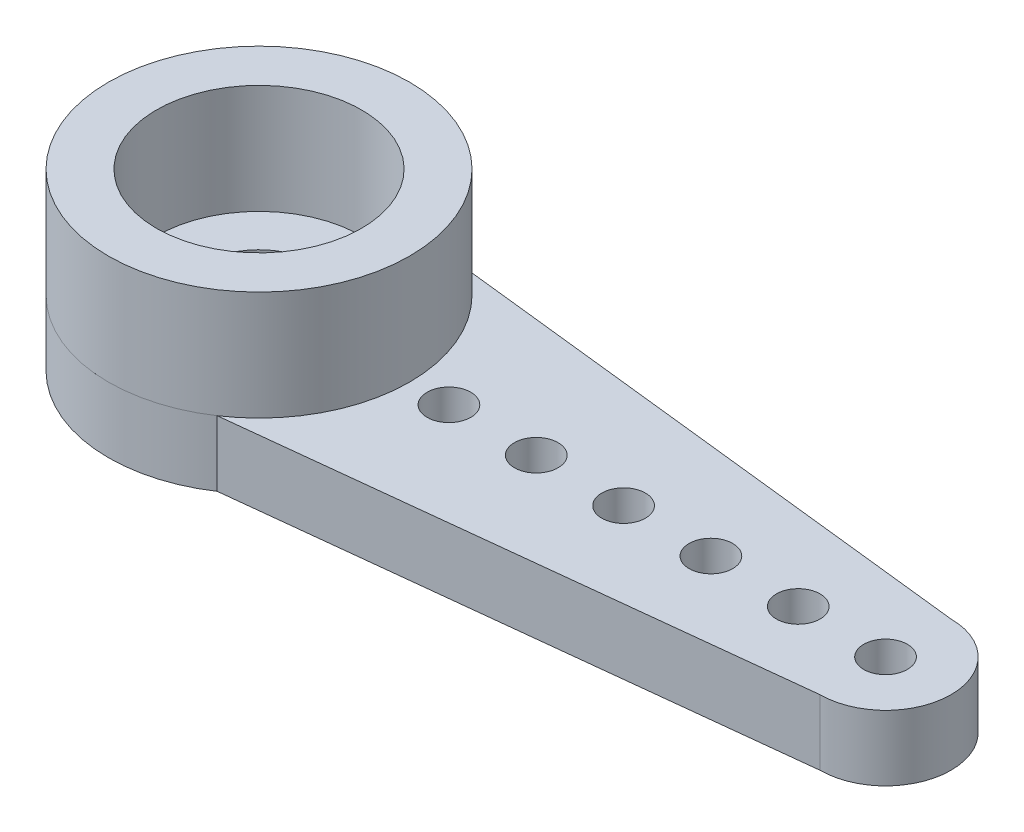
SolidWorks part; units mm, degrees
ref_plane "Front Plane" through (0, 0, 0) normal (0, 0, 1) x (1, 0, 0)
ref_plane "Top Plane" through (0, 0, 0) normal (0, 1, 0) x (1, 0, 0)
ref_plane "Right Plane" through (0, 0, 0) normal (1, 0, 0) x (0, 0, -1)
sketch "Sketch1" plane through (0, 0, 0) normal (0, 1, 0) x (1, 0, 0)
  line L0 (0, 0) -> (15.85, 0) construction
  line L1 (14.35, 1.5) -> (1.8797, 2.8929)
  line L3 (1.9132, -2.8709) -> (14.35, -1.5)
  arc A0 (1.8797, 2.8929) -> (1.9132, -2.8709) centre (0, 0) ccw
  circle A1 centre (0, 0) radius 1.275 construction
  circle A2 centre (0, 0) radius 2.35
  circle A4 centre (12.35, 0) radius 0.5
  circle A5 centre (14.35, 0) radius 0.5
  circle A6 centre (10.35, 0) radius 0.5
  circle A7 centre (8.35, 0) radius 0.5
  circle A9 centre (6.35, 0) radius 0.5
  circle A10 centre (4.35, 0) radius 0.5
  arc A11 (14.35, -1.5) -> (14.35, 1.5) centre (14.35, 0) ccw
  point P5 (0, 0)
  point P23 (0, 0)
  point P24 (0, 0)
  dimension "D1" = 14.35
  dimension "D2" = 2.55
  dimension "D3" = 4.7
  dimension "D4" = 6.9
sketch3d "3DSketch2" plane through (0, 0, 0) normal (0, 0, 1) x (1, 0, 0)
  dimension "D1" = 1.5
extrude "Boss-Extrude1" add sketch "Sketch1" along normal blind 1.5
sketch "Sketch2" plane through (0, 1.5, 0) normal (0, 1, 0) x (1, 0, 0)
  circle A0 centre (0, 0) radius 1.275
  circle A1 centre (0, 0) radius 2.35
  circle A2 centre (0, 0) radius 3.45
extrude "Boss-Extrude3" add sketch "Sketch2" against normal blind 0.5 separate body contours A1 A0 region at (-2.2835, 1.5, 0)
extrude "Boss-Extrude5" add sketch "Sketch2<7>" along normal blind 2.5 separate body contours A2 A1 region at (-3.3524, 1.5, 0)
sketch "Sketch2<7>" plane through (0, 1.5, 0) normal (0, 1, 0) x (1, 0, 0) same geometry as "Sketch2"
